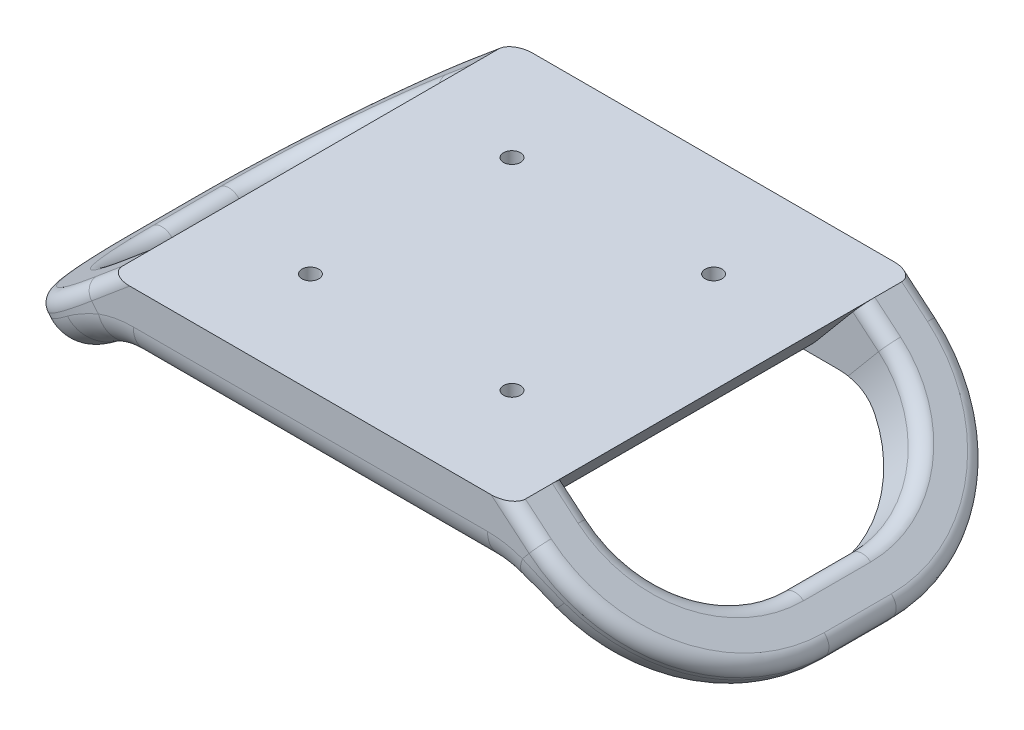
SolidWorks part; units mm, degrees
material "PET"
ref_plane "Front Plane" through (0, 0, 0) normal (0, 0, 1) x (1, 0, 0)
ref_plane "Top Plane" through (0, 0, 0) normal (0, 1, 0) x (1, 0, 0)
ref_plane "Right Plane" through (0, 0, 0) normal (1, 0, 0) x (0, 0, -1)
sketch "Sketch1" plane through (0, 0, 0) normal (0, 0, 1) x (1, 0, 0)
  line L0 (-19.05, 3.175) -> (-33.6431, -9.0701)
  line L1 (-19.05, -3.175) -> (19.05, -3.175)
  line L3 (-19.05, 3.175) -> (19.05, 3.175)
  line L5 (-19.05, -3.175) -> (19.05, 3.175) construction
  line L6 (-19.05, 3.175) -> (19.05, -3.175) construction
  line L7 (-33.6431, -9.0701) -> (-30.5164, -12.7964)
  line L8 (-30.5164, -12.7964) -> (-19.05, -3.175)
  line L9 (-19.05, 3.175) -> (-19.05, -3.175) construction
  line L10 (0, -1000) -> (0, 49000) construction
  line L11 (30.5164, -12.7964) -> (19.05, -3.175)
  line L12 (33.6431, -9.0701) -> (30.5164, -12.7964)
  line L13 (19.05, 3.175) -> (33.6431, -9.0701)
  point P0 (0, 0)
  dimension "D1" = 40
  dimension "D2" = 6.35
  dimension "D3" = 38.1
  dimension "D4" = 19.05
extrude "Main Body" add sketch "Sketch1" along normal blind 38.1
sketch "Sketch2" plane through (-9.4344, 11.2435, 0) normal (-0.6428, 0.766, 0) x (0.766, 0.6428, 0)
  line L0 (-26.5223, -22.225) -> (-26.5223, -15.875)
  line L1 (-15.7273, -5.08) -> (-12.5523, -5.08)
  line L2 (-31.6023, -38.1) -> (-31.6023, 0) construction
  line L3 (-12.5523, -33.02) -> (-15.7273, -33.02)
  line L4 (-1011.7033, -38.1) -> (48988.2967, -38.1) construction
  line L5 (-12.5523, -5.08) -> (-12.5523, -33.02)
  line L6 (-1012.5523, -19.05) -> (48987.4477, -19.05) construction
  line L7 (-12.5523, -38.1) -> (-12.5523, 0) construction
  line L8 (-31.6023, -15.875) -> (-31.6023, -22.225) construction
  line L9 (-15.7273, -15.875) -> (-15.7273, 0) construction
  line L10 (-12.5523, -1013.7143) -> (-12.5523, 48986.2857) construction
  line L11 (-15.7273, 0) -> (-12.5523, 0) construction
  line L12 (-15.7273, -38.1) -> (-12.5523, -38.1) construction
  line L13 (-15.7273, -38.1) -> (-31.6023, -38.1)
  line L14 (-31.6023, -38.1) -> (-31.6023, -22.225)
  line L15 (-15.7273, 0) -> (-31.6023, 0)
  line L16 (-31.6023, 0) -> (-31.6023, -15.875)
  arc A0 (-31.6023, -15.875) -> (-15.7273, 0) centre (-15.7273, -15.875) cw
  arc A1 (-31.6023, -22.225) -> (-15.7273, -38.1) centre (-15.7273, -22.225) ccw
  arc A2 (-26.5223, -15.875) -> (-15.7273, -5.08) centre (-15.7273, -15.875) cw
  arc A3 (-15.7273, -33.02) -> (-26.5223, -22.225) centre (-15.7273, -22.225) cw
  point P0 (-31.6023, -19.05)
  point P11 (-12.5523, -19.05)
  point P33 (-26.5223, -19.05)
  dimension "D1" = 3.175
  dimension "D2" = 5.08
  dimension "D3" = 5.08
  dimension "D4" = 3.175
  dimension "D5" = 5.08
extrude "Handle Cut 1" cut sketch "Sketch2" against normal through all
mirror "Handle Cut 2" about plane through (0, 0, 0) normal (1, 0, 0) of "Handle Cut 1"
sketch "Hole Locations" plane through (0, 3.175, 0) normal (0, 1, 0) x (1, 0, 0)
  line L0 (-1019.05, -19.05) -> (48980.95, -19.05) construction
  line L1 (-19.05, -33.02) -> (-19.05, -5.08) construction
  line L2 (0, -1000) -> (0, 49000) construction
  line L3 (19.05, 0) -> (-19.05, 0) construction
  line L5 (9.525, -28.575) -> (-9.525, -28.575)
  line L6 (9.525, -28.575) -> (9.525, -9.525)
  line L7 (9.525, -9.525) -> (-9.525, -9.525)
  line L8 (-9.525, -28.575) -> (-9.525, -9.525)
  line L9 (9.525, -28.575) -> (-9.525, -9.525) construction
  line L10 (9.525, -9.525) -> (-9.525, -28.575) construction
  point P5 (-19.05, -19.05)
  point P6 (0, -19.05)
  point P10 (0, 0)
  dimension "D1" = 19.05
  dimension "D2" = 19.05
hole_wizard "M2x0.4 Tapped Hole1" positions "Sketch6" profile "Sketch7" tap size "M2x0.4" standard "ANSI Metric" end condition through all
sketch "Sketch6" plane through (0, 3.175, 0) normal (0, 1, 0) x (1, 0, 0)
  point P0 (-9.525, -9.525)
  point P3 (9.525, -9.525)
  point P6 (9.525, -28.575)
  point P9 (-9.525, -28.575)
sketch "Sketch7" plane through (-9.525, 3.175, 9.525) normal (1, 0, 0) x (0, 0, 1)
  line L0 (0, 0) -> (0, 15.9714)
  line L1 (0, 15.9714) -> (0.8, 15.9714)
  line L2 (0.8, 15.9714) -> (0.8, 0)
  line L5 (0.8, 0) -> (0, 0)
  line L11 (0, -6.35) -> (0, 107.95) construction
  dimension "Thru Tap Drill Dia." = 1.6
  dimension "Thru Tap Drill Depth" = 15.9714
cosmetic thread "Hole Thread1" parameters "D2"=2
cosmetic thread "Hole Thread2" parameters "D2"=2
cosmetic thread "Hole Thread3" parameters "D2"=2
cosmetic thread "Hole Thread4" parameters "D2"=2
fillet "Fillet1" radius 6.35 4 edges at (19.05, -3.175, 35.528) (19.05, -3.175, 2.572) (-19.05, -3.175, 2.572) (-19.05, -3.175, 35.528)
fillet "Fillet2" radius 3.175 2 edges at (13.7217, -3.175, 19.05) (-13.7217, -3.175, 19.05)
fillet "Outside Rounding" radius 3.175 16 edges at (30.5164, -12.7964, 19.05) (27.7859, -10.5053, 32.2483) (19.6985, -3.9069, 37.989) (17.2675, -3.197, 38.1) (0, -3.175, 38.1) (-17.2675, -3.197, 38.1) (-19.1095, -3.6342, 38.0509) (-27.7859, -10.5053, 32.2483) (-30.5164, -12.7964, 19.05) (-27.7859, -10.5053, 5.8517) (-19.6985, -3.9069, 0.111) (-17.2675, -3.197, 0) (0, -3.175, 0) (17.2675, -3.197, 0) (19.1095, -3.6342, 0.0491) (27.7859, -10.5053, 5.8517)
fillet "Topside Rounding" radius 1.27 20 edges at (-20.2661, 2.1546, 5.08) (-27.3296, -3.7724, 8.2418) (-20.2661, 2.1546, 33.02) (-27.3296, -3.7724, 29.8582) (-20.2661, 2.1546, 38.1) (-30.0813, -6.0813, 33.4503) (-20.2661, 2.1546, 0) (-30.0813, -6.0813, 4.6497) (20.2661, 2.1546, 38.1) (30.0813, -6.0813, 33.4503) (33.6431, -9.0701, 19.05) (20.2661, 2.1546, 0) (20.2661, 2.1546, 5.08) (27.3296, -3.7724, 8.2418) (29.7516, -5.8047, 19.05) (20.2661, 2.1546, 33.02) (-29.7516, -5.8047, 19.05) (-33.6431, -9.0701, 19.05) (30.0813, -6.0813, 4.6497) (27.3296, -3.7724, 29.8582)
equation "\"D3@Sketch2\"=\"D2@Sketch2\""
equation "\"D4@Sketch2\"=\"D1@Sketch2\""
equation "\"D5@Sketch2\"=\"D3@Sketch2\""
